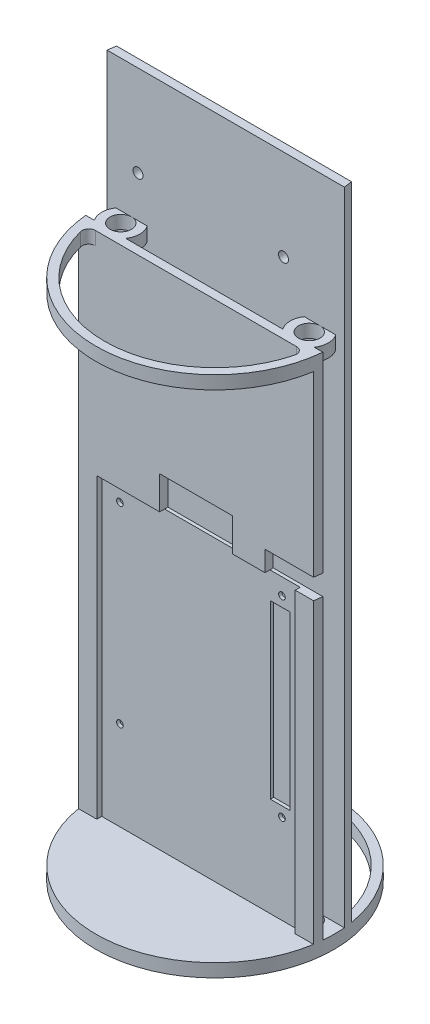
SolidWorks part; units mm, degrees
ref_plane "Front Plane" through (0, 0, 0) normal (0, 0, 1) x (1, 0, 0)
ref_plane "Top Plane" through (0, 0, 0) normal (0, 1, 0) x (1, 0, 0)
ref_plane "Right Plane" through (0, 0, 0) normal (1, 0, 0) x (0, 0, -1)
sketch "Sketch1" plane through (0, 0, 0) normal (0, 1, 0) x (1, 0, 0)
  circle A0 centre (0, 0) radius 36
  dimension "D1" = 72
extrude "Boss-Extrude1" add sketch "Sketch1" along normal blind 4
sketch "Sketch2" plane through (0, 4, 0) normal (0, 1, 0) x (1, 0, 0)
  line L0 (-36.3097, 0) -> (36, 0) construction
  line L1 (35.5378, -5.75) -> (-35.5378, -5.75)
  line L2 (35.5378, -5.75) -> (35.5378, 5.75)
  line L3 (35.5378, 5.75) -> (-35.5378, 5.75)
  line L4 (-35.5378, -5.75) -> (-35.5378, 5.75)
  line L5 (35.5378, -5.75) -> (-35.5378, 5.75) construction
  line L6 (35.5378, 5.75) -> (-35.5378, -5.75) construction
  line L7 (35.853, -3.25) -> (-35.853, -3.25)
  line L8 (35.853, -3.25) -> (35.853, 3.25)
  line L9 (35.853, 3.25) -> (-35.853, 3.25)
  line L10 (-35.853, -3.25) -> (-35.853, 3.25)
  line L11 (35.853, -3.25) -> (-35.853, 3.25) construction
  line L12 (35.853, 3.25) -> (-35.853, -3.25) construction
  circle A0 centre (-28.5, 0) radius 3.25
  circle A1 centre (0, 0) radius 36
  circle A2 centre (0, 0) radius 36
  circle A3 centre (28.5, 0) radius 3.25
  circle A4 centre (-28.5, 0) radius 5.75
  circle A5 centre (28.5, 0) radius 5.75
  circle M4 centre (0, 0) radius 36
  dimension "D5" = 28.5
  dimension "D2" = 11.5
  dimension "D3" = 6.5
  dimension "D4" = 57
  dimension "D1" = 0
extrude "Boss-Extrude2" add sketch "Sketch2" along normal blind 90 contours L9 A4 | A4 L3 L4 L9 | A5 L3 A4 L9 | L9 A5 | A5 L9 L2 L3 | A5 L1 L2 L7 | A5 L7 | A5 L7 A4 L1 | A4 L7 | A4 L7 L4 L1 | L9 L4 M4 | L4 L7 M4 | L9 L2 M4 | L7 L2 M4 region at (33.5238, 4, 4.7055) region at (35.6482, 4, 4.1192) region at (0, 4, 4.5303) region at (28.5, 4, 4.2713) region at (-33.5238, 4, 4.7055) region at (-35.6482, 4, 4.1192) region at (-28.5, 4, 4.2713) region at (33.5238, 4, -4.7055) region at (35.6482, 4, -4.1192) region at (28.5, 4, -4.2713) region at (0, 4, -4.5303) region at (-35.6482, 4, -4.1192) region at (-33.5238, 4, -4.7055) region at (-28.5, 4, -4.2713)
sketch "Sketch4" plane through (0, 4, 0) normal (0, 1, 0) x (1, 0, 0)
  circle A0 centre (-28.5, 0) radius 3.25
  circle A1 centre (28.5, 0) radius 3.25
  dimension "D1" = 6.5
  dimension "D2" = 6.5
  dimension "D3" = 57
  dimension "D4" = 28.5
extrude "Cut-Extrude2" cut sketch "Sketch4" against normal blind 10
sketch "Sketch3" plane through (0, 94, 0) normal (0, 1, 0) x (1, 0, 0)
  line L0 (35.5378, -5.75) -> (-35.5378, -5.75) construction
  line L1 (-30, -5.75) -> (30, -5.75)
  line L2 (-30, -5.75) -> (-30, -4.25)
  line L3 (-30, -4.25) -> (30, -4.25)
  line L4 (30, -5.75) -> (30, -4.25)
  point P6 (-30, -5)
  dimension "D1" = 1.5
  dimension "D2" = 30
  dimension "D3" = 60
extrude "Cut-Extrude1" cut sketch "Sketch3" against normal blind 90
sketch "Sketch6" plane through (0, 0, 4.25) normal (0, 0, 1) x (1, 0, 0)
  line L0 (30, 4) -> (30, 94) construction
  line L1 (27, 86) -> (21, 86)
  line L2 (27, 86) -> (27, 34)
  line L3 (27, 34) -> (21, 34)
  line L4 (21, 86) -> (21, 34)
  line L5 (30, 94) -> (-30, 94) construction
  dimension "D1" = 6
  dimension "D2" = 3
  dimension "D3" = 8
  dimension "D4" = 52
extrude "Cut-Extrude4" cut sketch "Sketch6" against normal blind 5
sketch "Sketch7" plane through (0, 0, 4.25) normal (0, 0, 1) x (1, 0, 0)
  line L0 (30, 94) -> (-30, 94) construction
  line L1 (-30, 4) -> (-30, 94) construction
  circle A0 centre (-24.5, 89) radius 1
  circle A1 centre (24.5, 89) radius 1
  circle A2 centre (24.5, 31) radius 1
  circle A3 centre (-24.5, 31) radius 1
  dimension "D1" = 2
  dimension "D2" = 5
  dimension "D5" = 5.5
  dimension "D3" = 2
  dimension "D4" = 2
extrude "Cut-Extrude5" cut sketch "Sketch7" against normal blind 5 contours A1 | A2 | A3 | A0 region at (24.5, 89, 4.25) region at (24.5, 31, 4.25) region at (-24.5, 31, 4.25)
sketch "Sketch9" plane through (0, 94, 0) normal (0, 1, 0) x (1, 0, 0)
  line L0 (35.853, 3.25) -> (-35.853, 3.25) construction
  line L1 (-28.5, 3.25) -> (-35.853, 3.25) construction
  line L2 (35.5378, 5.75) -> (-35.5378, 5.75) construction
  line L3 (35.853, 3.25) -> (-35.853, 3.25)
  line L4 (-28.5, 3.25) -> (-35.853, 3.25)
  line L5 (35.5378, 5.75) -> (-35.5378, 5.75)
  line L6 (-30, -5.75) -> (-30, -4.25)
  line L7 (-30, -4.25) -> (30, -4.25)
  line L8 (30, -4.25) -> (30, -5.75)
  line L9 (30, -5.75) -> (35.5378, -5.75)
  line L10 (35.853, -3.25) -> (-35.853, -3.25)
  line L11 (-35.5378, -5.75) -> (-30, -5.75)
  line L15 (30, -5.75) -> (35.5378, -5.75)
  line L16 (35.853, -3.25) -> (-35.853, -3.25)
  line L17 (-35.5378, -5.75) -> (-30, -5.75)
  line L18 (-30, -5.75) -> (30, -5.75)
  arc A0 (-35.5378, 5.75) -> (-35.853, 3.25) centre (0, 0) ccw construction
  arc A1 (35.853, 3.25) -> (35.5378, 5.75) centre (0, 0) ccw construction
  arc A2 (35.5378, -5.75) -> (35.853, -3.25) centre (0, 0) ccw
  arc A3 (-35.853, -3.25) -> (-35.5378, -5.75) centre (0, 0) ccw
  arc A4 (35.5378, -5.75) -> (35.853, -3.25) centre (0, 0) ccw
  arc A5 (-35.853, -3.25) -> (-35.5378, -5.75) centre (0, 0) ccw
  arc A6 (-35.5378, 5.75) -> (-35.853, 3.25) centre (0, 0) ccw
  arc A7 (35.853, 3.25) -> (35.5378, 5.75) centre (0, 0) ccw
  line M9 (-30, -5.75) -> (-30, -4.25)
  line M10 (-30, -4.25) -> (30, -4.25)
  line M11 (30, -4.25) -> (30, -5.75)
  line M12 (30, -5.75) -> (35.5378, -5.75)
  arc M13 (35.5378, -5.75) -> (35.853, -3.25) centre (0, 0) ccw
  line M14 (35.853, -3.25) -> (-35.853, -3.25)
  arc M15 (-35.853, -3.25) -> (-35.5378, -5.75) centre (0, 0) ccw
  line M16 (-35.5378, -5.75) -> (-30, -5.75)
  dimension "D1" = 0
extrude "Boss-Extrude3" add sketch "Sketch9" along normal blind 60 contours L3 A7 L5 A6 | M16 M9 M10 M11 M12 M13 M14 M15 | L18 M9 M11 M10 region at (0, 94, -4.4982) region at (0, 94, 3.9881) region at (0, 94, 5)
sketch "Sketch10" plane through (0, 0, 5.75) normal (0, 0, 1) x (1, 0, 0)
  line L0 (30, 94) -> (-30, 94) construction
  line L1 (11, 94) -> (-11, 94)
  line L2 (11, 94) -> (11, 104)
  line L3 (11, 104) -> (-11, 104)
  line L4 (-11, 94) -> (-11, 104)
  line L5 (11, 94) -> (-11, 104) construction
  line L6 (11, 104) -> (-11, 94) construction
  point P4 (0, 99)
  dimension "D1" = 22
  dimension "D2" = 10
extrude "Cut-Extrude6" cut sketch "Sketch10" against normal blind 5 contours L4 L3 L2 L1
sketch "Sketch11" plane through (0, 154, 0) normal (0, 1, 0) x (1, 0, 0)
  line L5 (-35.5378, -5.75) -> (35.5378, -5.75) construction
  line L6 (-23.7566, 3.25) -> (23.7566, 3.25)
  line L7 (35.853, 3.25) -> (28.5, 3.25) construction
  line L8 (35.5378, 5.75) -> (-35.5378, 5.75) construction
  line L9 (35.853, -3.25) -> (-35.853, -3.25) construction
  line L10 (-28.5, 3.25) -> (-35.853, 3.25) construction
  line L11 (-35.853, -3.25) -> (-28.5, -3.25) construction
  line L12 (-35.853, 3.25) -> (35.853, 3.25) construction
  line L13 (-30.4305, -5.75) -> (30.4305, -5.75)
  line L14 (-28.5, -3.25) -> (28.5, -3.25) construction
  line L15 (28.5, 3.25) -> (-28.5, 3.25) construction
  line L18 (-33.2434, -3.25) -> (-35.853, -3.25)
  line L21 (30.4305, 5.75) -> (-30.4305, 5.75)
  line L23 (35.853, 3.25) -> (33.2434, 3.25)
  line L25 (35.853, -3.25) -> (28.5, -3.25)
  line L26 (-33.2434, 3.25) -> (-35.853, 3.25)
  line L27 (-35.853, -3.25) -> (-33.2434, -3.25)
  line L28 (-35.853, 3.25) -> (28.5, 3.25)
  line L30 (-23.7566, -3.25) -> (23.7566, -3.25)
  line L31 (28.5, 3.25) -> (-28.5, 3.25)
  line L32 (23.7566, -3.25) -> (-23.7566, -3.25)
  line L33 (33.2434, 3.25) -> (35.853, 3.25)
  arc A0 (-35.5378, -5.75) -> (35.5378, -5.75) centre (0, 0) ccw construction
  arc A1 (35.5378, 5.75) -> (-35.5378, 5.75) centre (0, 0) ccw construction
  arc A2 (28.5, -3.25) -> (28.5, 3.25) centre (28.5, 0) ccw construction
  arc A3 (35.853, -3.25) -> (35.853, 3.25) centre (0, 0) ccw construction
  arc A4 (35.5378, -5.75) -> (35.853, -3.25) centre (0, 0) ccw construction
  arc A5 (-35.853, -3.25) -> (-35.5378, -5.75) centre (0, 0) ccw construction
  arc A6 (-28.5, 3.25) -> (-28.5, -3.25) centre (-28.5, 0) ccw construction
  arc A7 (-35.853, 3.25) -> (-35.853, -3.25) centre (0, 0) ccw construction
  arc A8 (35.853, 3.25) -> (35.5378, 5.75) centre (0, 0) ccw construction
  arc A9 (-35.5378, 5.75) -> (-35.853, 3.25) centre (0, 0) ccw construction
  arc A10 (-28.5, -3.25) -> (-28.5, 3.25) centre (-28.5, 0) ccw construction
  arc A11 (28.5, 3.25) -> (28.5, -3.25) centre (28.5, 0) ccw construction
  arc A12 (-35.5378, -5.75) -> (35.5378, -5.75) centre (0, 0) ccw
  arc A13 (35.5378, 5.75) -> (-35.5378, 5.75) centre (0, 0) ccw
  arc A14 (28.5, -3.25) -> (28.5, 3.25) centre (28.5, 0) ccw
  arc A15 (35.853, -3.25) -> (35.853, 3.25) centre (0, 0) ccw
  arc A16 (35.5378, -5.75) -> (35.853, -3.25) centre (0, 0) ccw
  arc A17 (-35.853, -3.25) -> (-35.5378, -5.75) centre (0, 0) ccw
  arc A18 (-28.5, 3.25) -> (-28.5, -3.25) centre (-28.5, 0) ccw
  arc A19 (-35.853, 3.25) -> (-35.853, -3.25) centre (0, 0) ccw
  arc A20 (35.853, 3.25) -> (35.5378, 5.75) centre (0, 0) ccw
  arc A21 (-35.5378, 5.75) -> (-35.853, 3.25) centre (0, 0) ccw
  arc A22 (-28.5, -3.25) -> (-28.5, 3.25) centre (-28.5, 0) ccw
  arc A23 (28.5, 3.25) -> (28.5, -3.25) centre (28.5, 0) ccw
  arc A24 (-33.2434, 3.25) -> (-33.2434, -3.25) centre (-28.5, 0) ccw
  arc A25 (23.7566, 3.25) -> (23.7566, -3.25) centre (28.5, 0) ccw
  arc A28 (-23.7566, -3.25) -> (-23.7566, 3.25) centre (-28.5, 0) ccw
  arc A29 (-32.3687, -8.2436) -> (32.3687, -8.2436) centre (0, 0) ccw
  arc A30 (33.2434, -3.25) -> (33.2434, 3.25) centre (28.5, 0) ccw
  arc A32 (32.3687, 8.2436) -> (-32.3687, 8.2436) centre (0, 0) ccw
  arc A33 (30.4305, -5.75) -> (32.3687, -8.2436) centre (30.4305, -7.75) cw
  arc A34 (-30.4305, -5.75) -> (-32.3687, -8.2436) centre (-30.4305, -7.75) ccw
  arc A35 (-32.3687, 8.2436) -> (-30.4305, 5.75) centre (-30.4305, 7.75) ccw
  arc A36 (32.3687, 8.2436) -> (30.4305, 5.75) centre (30.4305, 7.75) cw
  line M1 (-35.853, 3.25) -> (35.853, 3.25)
  arc M2 (35.853, 3.25) -> (35.5378, 5.75) centre (0, 0) ccw
  line M3 (35.5378, 5.75) -> (-35.5378, 5.75)
  arc M4 (-35.5378, 5.75) -> (-35.853, 3.25) centre (0, 0) ccw
  dimension "D1" = 2
  dimension "D2" = 2
  dimension "D3" = 2
extrude "Boss-Extrude4" add sketch "Sketch11" along normal blind 4 contours L28 M4 M1 M2 M3 | L30 A28 L28 A22 A18 A24 L18 A17 A12 A16 L25 A23 A25 A34 L13 A33 A29 M1 | L25 A30 A14 M1 region at (0, 154, -4.4982) region at (-23.5675, 154, 0) region at (32.4135, 154, 0)
sketch "Sketch12" plane through (0, 158, 0) normal (0, 1, 0) x (1, 0, 0)
  line L8 (35.5378, 5.75) -> (-35.5378, 5.75)
  line L9 (-35.853, 3.25) -> (35.853, 3.25)
  arc A4 (35.853, 3.25) -> (35.5378, 5.75) centre (0, 0) ccw construction
  arc A5 (-35.5378, 5.75) -> (-35.853, 3.25) centre (0, 0) ccw construction
  arc A6 (35.853, 3.25) -> (35.5378, 5.75) centre (0, 0) ccw
  arc A7 (-35.5378, 5.75) -> (-35.853, 3.25) centre (0, 0) ccw
extrude "Boss-Extrude5" add sketch "Sketch12" along normal blind 40 contours L8 A7 L9 A6
sketch "Sketch13" plane through (0, 0, 5.75) normal (0, 0, 1) x (1, 0, 0)
  line L0 (35.853, 158) -> (35.853, 4) construction
  line L1 (35.853, 94) -> (20.853, 94)
  line L2 (35.853, 94) -> (35.853, 100.1572)
  line L3 (35.853, 100.1572) -> (20.853, 100.1572)
  line L4 (20.853, 94) -> (20.853, 100.1572)
  dimension "D1" = 15
extrude "Cut-Extrude8" cut sketch "Sketch13" against normal blind 4
sketch "Sketch8" plane through (0, 0, -5.75) normal (0, 0, -1) x (-1, 0, 0)
  line L1 (-17.4622, 82.5) -> (26.5378, 82.5)
  line L2 (-17.4622, 82.5) -> (-17.4622, 170.5)
  line L3 (-17.4622, 170.5) -> (26.5378, 170.5)
  line L4 (26.5378, 82.5) -> (26.5378, 170.5)
  line L5 (-17.4622, 82.5) -> (26.5378, 170.5) construction
  line L6 (-17.4622, 170.5) -> (26.5378, 82.5) construction
  line L8 (-35.5378, 198) -> (35.5378, 198) construction
  line L9 (35.5378, 198) -> (35.5378, 4) construction
  circle A0 centre (-17.4622, 170.5) radius 1.5
  circle A1 centre (26.5378, 170.5) radius 1.5
  circle A2 centre (26.5378, 82.5) radius 1.5
  circle A3 centre (-17.4622, 82.5) radius 1.5
  point P3 (4.5378, 126.5)
  dimension "D1" = 3
  dimension "D5" = 9
  dimension "D4" = 27.5
  dimension "D2" = 2
  dimension "D3" = 2
extrude "Cut-Extrude7" cut sketch "Sketch8" against normal blind 5 contours A3 | A2 | A1 | A0
sketch "Sketch15" plane through (0, 0, 0) normal (0, -1, 0) x (1, 0, 0)
  line L1 (23.7566, -3.25) -> (-23.7566, -3.25)
  line L3 (23.7566, 3.25) -> (-23.7566, 3.25)
  line L5 (28.5, -3.25) -> (-28.5, 3.25) construction
  line L6 (28.5, 3.25) -> (-28.5, -3.25) construction
  line L7 (30.4443, -5.75) -> (-30.4443, -5.75)
  line L9 (30.4443, 5.75) -> (-30.4443, 5.75)
  line L11 (35.5533, -5.75) -> (-35.5533, 5.75) construction
  line L12 (35.5533, 5.75) -> (-35.5533, -5.75) construction
  circle A0 centre (0, 0) radius 36.0153
  circle A1 centre (-28.5, 0) radius 3.25
  circle A2 centre (-28.5, 0) radius 3.25
  circle A3 centre (28.5, 0) radius 3.25
  circle A4 centre (-28.5, 0) radius 5.75
  circle A5 centre (28.5, 0) radius 5.75
  arc A6 (32.3825, 8.2434) -> (-32.3825, 8.2434) centre (0, 0) ccw
  arc A7 (-30.4443, 5.75) -> (-32.3825, 8.2434) centre (-30.4443, 7.75) cw
  arc A8 (-30.4443, -5.75) -> (-32.3825, -8.2434) centre (-30.4443, -7.75) ccw
  arc A9 (-32.3825, -8.2434) -> (32.3825, -8.2434) centre (0, 0) ccw
  arc A10 (30.4443, -5.75) -> (32.3825, -8.2434) centre (30.4443, -7.75) cw
  arc A11 (32.3825, 8.2434) -> (30.4443, 5.75) centre (30.4443, 7.75) cw
  dimension "D1" = 6.5
  dimension "D2" = 6.5
  dimension "D4" = 2.6
  dimension "D5" = 2
  dimension "D3" = 2.5
extrude "Cut-Extrude9" cut sketch "Sketch15" against normal blind 5 contours A5 L3 A4 L1 | L7 A8 A9 A10 region at (0, 0, 0)
